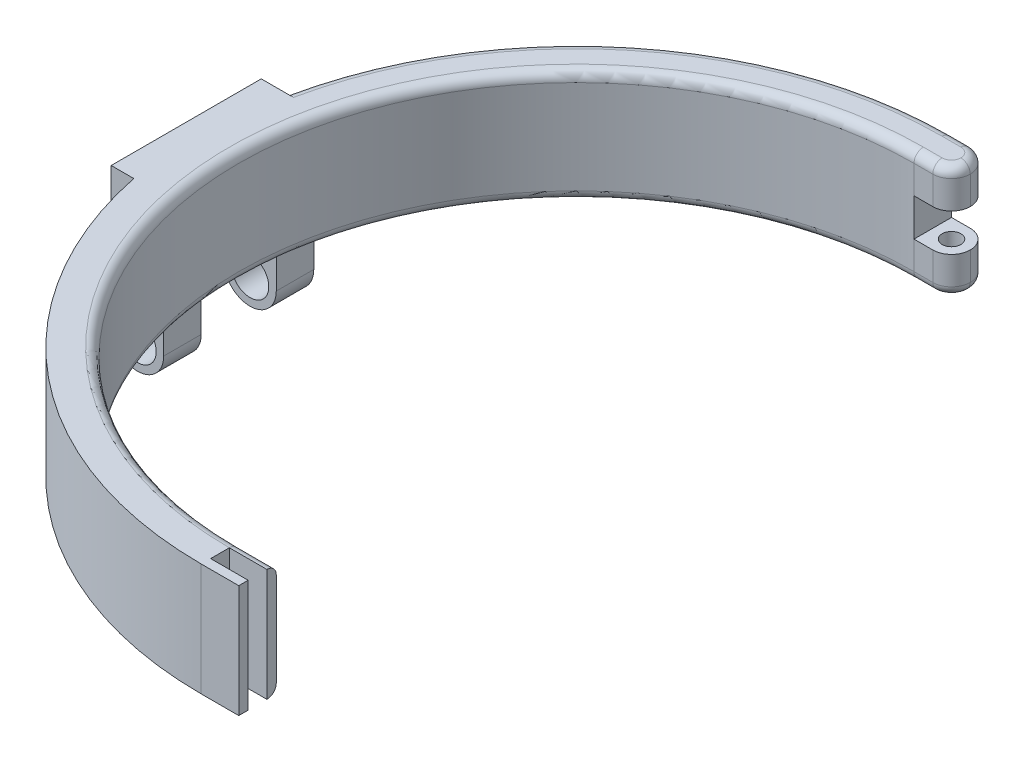
SolidWorks part; units mm, degrees
ref_plane "Front Plane" through (0, 0, 0) normal (0, 0, 1) x (1, 0, 0)
ref_plane "Top Plane" through (0, 0, 0) normal (0, 1, 0) x (1, 0, 0)
ref_plane "Right Plane" through (0, 0, 0) normal (1, 0, 0) x (0, 0, -1)
sketch "Sketch1" plane through (0, 0, 0) normal (0, 1, 0) x (1, 0, 0)
  line L0 (0, 100) -> (0, 90)
  line L1 (0, -90) -> (0, -100)
  arc A0 (0, 90) -> (0, -90) centre (0, 0) ccw
  arc A1 (0, 100) -> (0, -100) centre (0, 0) ccw
  dimension "D1" = 90
  dimension "D2" = 100
extrude "Boss-Extrude1" add sketch "Sketch1" along normal blind 30
sketch "Sketch2" plane through (0, 0, 0) normal (0, -1, 0) x (1, 0, 0)
  line L1 (-90, -20) -> (-104, -20)
  line L2 (-90, -20) -> (-90, 20)
  line L3 (-90, 20) -> (-104, 20)
  line L4 (-104, -20) -> (-104, 20)
  arc A0 (0, 100) -> (0, -100) centre (0, 0) ccw construction
  point P4 (-100, 0)
  point P8 (-100, 0)
  dimension "D1" = 40
  dimension "D2" = 14
  dimension "D3" = 20
  dimension "D4" = 4
extrude "Boss-Extrude2" add sketch "Sketch2" along normal blind 14 and the other way through all
sketch "Sketch3" plane through (0, -14, 0) normal (0, -1, 0) x (1, 0, 0)
  line L0 (-90, -20) -> (-90, 20) construction
  line L1 (-90, 10) -> (-104, 10)
  line L2 (-90, 10) -> (-90, -10)
  line L3 (-90, -10) -> (-104, -10)
  line L4 (-104, 10) -> (-104, -10)
  line L5 (-104, 20) -> (-104, -20) construction
  line L6 (-90, 20) -> (-104, 20) construction
  dimension "D1" = 20
  dimension "D2" = 10
extrude "Cut-Extrude1" cut sketch "Sketch3" against normal blind 14
sketch "Sketch5" plane through (0, 0, 0) normal (0, 0, 1) x (1, 0, 0)
  circle A0 centre (-97, -7) radius 5
  dimension "D1" = 10
extrude "Cut-Extrude2" cut sketch "Sketch5" against normal blind 20 and the other way blind 20
sketch "Sketch6" plane through (0, 0, 0) normal (1, 0, 0) x (0, 0, -1)
  line L0 (100, 30) -> (100, 0) construction
  line L1 (90, 30) -> (100, 30)
  line L2 (90, 30) -> (90, 20)
  line L3 (90, 20) -> (100, 20)
  line L4 (100, 30) -> (100, 20)
  line L5 (90, 30) -> (90, 0) construction
  line L6 (100, 0) -> (90, 0)
  line L7 (100, 0) -> (100, 10)
  line L8 (100, 10) -> (90, 10)
  line L9 (90, 0) -> (90, 10)
  dimension "D1" = 10
  dimension "D2" = 10
extrude "Boss-Extrude3" add sketch "Sketch6" along normal blind 10
sketch "Sketch7" plane through (0, 10, 0) normal (0, 1, 0) x (1, 0, 0)
  circle A0 centre (5, 95) radius 2.5
  dimension "D1" = 5
extrude "Cut-Extrude3" cut sketch "Sketch7" against normal blind 5 and the other way blind 15
sketch "Sketch8" plane through (0, 0, 0) normal (1, 0, 0) x (0, 0, -1)
  line L1 (-100, 0) -> (-90, 0)
  line L2 (-100, 0) -> (-100, 30)
  line L3 (-100, 30) -> (-90, 30)
  line L4 (-90, 0) -> (-90, 30)
extrude "Boss-Extrude4" add sketch "Sketch8" along normal blind 10
sketch "Sketch9" plane through (10, 0, 0) normal (1, 0, 0) x (0, 0, -1)
  line L0 (-90, 30) -> (-100, 30) construction
  line L1 (-97.5, 30) -> (-92.5, 30)
  line L2 (-97.5, 30) -> (-97.5, 0)
  line L3 (-97.5, 0) -> (-92.5, 0)
  line L4 (-92.5, 30) -> (-92.5, 0)
  line L5 (-100, 0) -> (-90, 0) construction
  line L6 (-100, 30) -> (-100, 0) construction
  dimension "D1" = 5
  dimension "D2" = 2.5
extrude "Cut-Extrude4" cut sketch "Sketch9" against normal blind 10
sketch "Sketch10" plane through (-104, 0, 0) normal (-1, 0, 0) x (0, 0, 1)
  circle A0 centre (0, 15) radius 10
  dimension "D1" = 20
extrude "Cut-Extrude5" cut sketch "Sketch10" against normal blind 5
sketch "Sketch11" plane through (-99, 0, 0) normal (-1, 0, 0) x (0, 0, 1)
  circle A0 centre (0, 15) radius 12
  dimension "D1" = 24
extrude "Cut-Extrude6" cut sketch "Sketch11" against normal blind 5
fillet "Fillet1" radius 7 4 edges at (-104, -14, -15) (-90, -14, -15) (-104, -14, 15) (-90, -14, 15)
fillet "Fillet3" radius 5 4 edges at (10, 5, -90) (10, 5, -100) (10, 25, -100) (10, 25, -90)
fillet "Fillet2" radius 2.5 14 edges at (5, 0, 90) (2.5, 0, -90) (5, 30, 90) (2.5, 30, -90) (-90, 0, 0) (-90, 30, 0) (-63.2456, 0, -77.4597) (2.5, 0, -100) (8.5355, 0, -98.5355) (8.5355, 0, -91.4645) (-63.2456, 30, -77.4597) (2.5, 30, -100) (8.5355, 30, -98.5355) (8.5355, 30, -91.4645)
